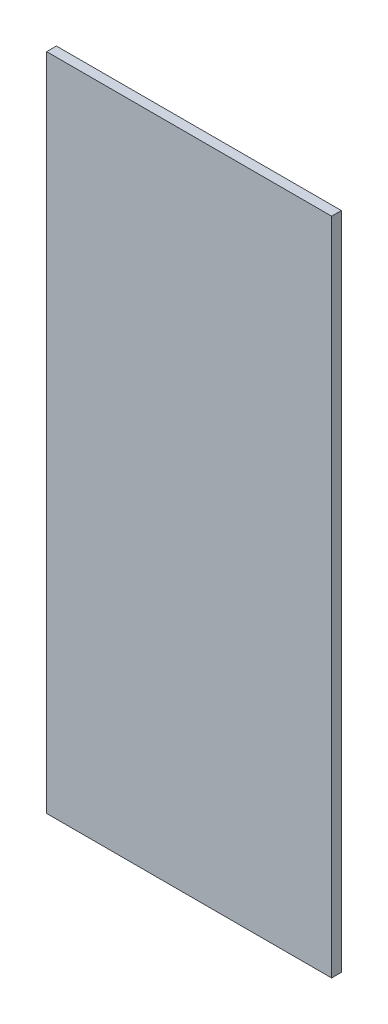
SolidWorks part; units mm, degrees
material "PC High Viscosity"
ref_plane "Front Plane" through (0, 0, 0) normal (0, 0, 1) x (1, 0, 0)
ref_plane "Top Plane" through (0, 0, 0) normal (0, 1, 0) x (1, 0, 0)
ref_plane "Right Plane" through (0, 0, 0) normal (1, 0, 0) x (0, 0, -1)
sketch "Sketch1" plane through (0, 0, 0) normal (0, 0, 1) x (1, 0, 0)
  line L1 (-73, -169) -> (73, -169)
  line L2 (-73, -169) -> (-73, 169)
  line L3 (-73, 169) -> (73, 169)
  line L4 (73, -169) -> (73, 169)
  line L5 (-73, -169) -> (73, 169) construction
  line L6 (-73, 169) -> (73, -169) construction
  point P0 (0, 0)
  dimension "D1" = 146
  dimension "D2" = 338
extrude "Boss-Extrude1" add sketch "Sketch1" along normal mid plane 5
sketch "Sketch2" [suppressed] plane through (0, 0, 2.5) normal (0, 0, 1) x (1, 0, 0)
  line L0 (106, 171) -> (104, 171) construction
  line L1 (-155.214, 211.8255) -> (203.9552, 211.8255)
  line L2 (-155.214, 211.8255) -> (-155.214, 171)
  line L3 (-155.214, 171) -> (203.9552, 171)
  line L4 (203.9552, 211.8255) -> (203.9552, 171)
extrude "Cut-Extrude1" [suppressed] cut sketch "Sketch2" against normal through all
